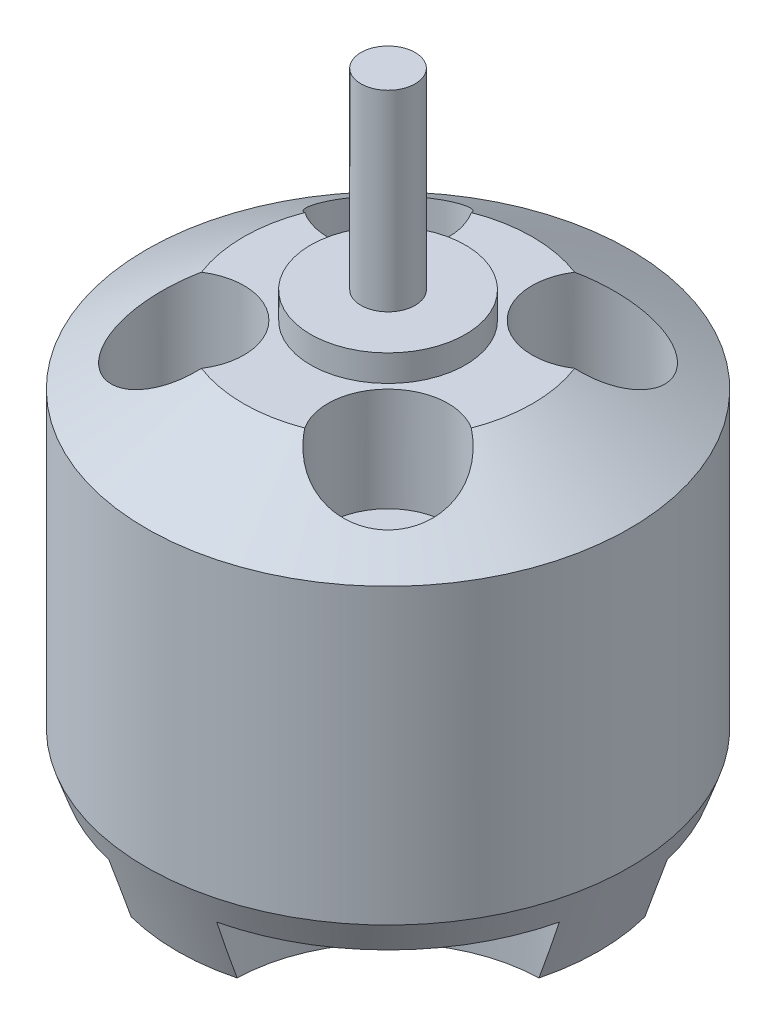
SolidWorks part; units mm, degrees
ref_plane "Front Plane" through (0, 0, 0) normal (0, 0, 1) x (1, 0, 0)
ref_plane "Top Plane" through (0, 0, 0) normal (0, 1, 0) x (1, 0, 0)
ref_plane "Right Plane" through (0, 0, 0) normal (1, 0, 0) x (0, 0, -1)
sketch "Sketch1" plane through (0, 0, 0) normal (0, 0, 1) x (1, 0, 0)
  line L0 (6.9564, -8.4455) -> (5.1721, -13.5255)
  line L1 (-6.9564, 8.4455) -> (6.9564, 8.4455)
  line L2 (-6.9564, 8.4455) -> (-6.9564, -8.4455)
  line L3 (-6.9564, -8.4455) -> (6.9564, -8.4455)
  line L4 (6.9564, 8.4455) -> (6.9564, -8.4455)
  line L5 (-6.9564, 8.4455) -> (6.9564, -8.4455) construction
  line L6 (-6.9564, -8.4455) -> (6.9564, 8.4455) construction
  line L7 (5.1721, -13.5255) -> (-6.9564, -13.5255)
  line L8 (-6.9564, -13.5255) -> (-6.9564, -8.4455)
  line L9 (6.9564, 8.4455) -> (1.3621, 11.8745)
  line L10 (1.3621, 11.8745) -> (-6.9564, 11.8745)
  line L11 (-6.9564, 11.8745) -> (-6.9564, 8.4455)
  line L12 (-6.9564, 11.8745) -> (-6.9564, 13.3985)
  line L13 (-6.9564, 13.3985) -> (-2.4987, 13.3985)
  line L14 (-2.4987, 13.3985) -> (-2.4987, 11.8745)
  line L16 (-5.3943, 13.3985) -> (-5.3943, 24.4475)
  line L17 (-5.3943, 24.4475) -> (-6.9564, 24.4475)
  line L18 (-6.9564, 24.4475) -> (-6.9564, 13.3985)
  line L19 (-6.9564, -13.5255) -> (-6.9564, -14.7955)
  line L20 (-6.9564, -14.7955) -> (-5.3943, -14.7955)
  line L21 (-5.3943, -14.7955) -> (-5.3943, -13.5255)
  point P0 (0, 0)
  dimension "D1" = 16.891
  dimension "D2" = 8.3185
  dimension "D3" = 5.08
  dimension "D4" = 25.4
  dimension "D5" = 1.524
  dimension "D6" = 11.049
  dimension "D7" = 1.27
  dimension "D8" = 13.9128
  dimension "D9" = 4.4577
  dimension "D10" = 1.5621
  dimension "D11" = 1.5621
  dimension "D12" = 12.1285
revolve "Revolve1" add sketch "Sketch1" angle 360 about L2 region at (-0.4359, -10.9275, 0) region at (0, 0, 0) region at (-1.2813, 10.0162, 0) region at (-6.1754, -14.1605, 0) region at (-4.7276, 12.6365, 0) region at (-6.1754, 18.923, 0)
sketch "Sketch2" plane through (0, -13.5255, 0) normal (0, -1, 0) x (1, 0, 0)
  line L0 (-6.9564, 11.9576) -> (-6.9564, -11.9576) construction
  line L1 (-18.914, 11.9576) -> (5.0012, 11.9576) construction
  line L2 (-18.914, 11.9576) -> (-18.914, -11.9576) construction
  line L3 (-18.914, -11.9576) -> (5.0012, -11.9576) construction
  line L4 (5.0012, 11.9576) -> (5.0012, -11.9576) construction
  line L5 (-18.914, 11.9576) -> (5.0012, -11.9576) construction
  line L6 (-18.914, -11.9576) -> (5.0012, 11.9576) construction
  line L8 (5.0012, 0) -> (-18.914, 0) construction
  circle A0 centre (5.0012, 11.9576) radius 8.9096
  circle A1 centre (-18.914, 11.9576) radius 8.9096
  circle A2 centre (-18.914, -11.9576) radius 8.9096
  circle A3 centre (5.0012, -11.9576) radius 8.9096
  circle A4 centre (-6.9564, 9.4488) radius 1.27
  circle A5 centre (2.7718, 0) radius 1.27
  circle A6 centre (-6.9564, -9.4488) radius 1.27
  circle A7 centre (-16.6846, 0) radius 1.27
  point P0 (-6.9564, 0)
  point P10 (-10.0044, 11.9576)
  point P11 (-3.9084, 11.9576)
  point P12 (-12.614, -5.6576)
  point P13 (-1.2989, 5.6576)
  dimension "D2" = 2.54
  dimension "D1" = 9.4488
  dimension "D3" = 9.4488
  dimension "D4" = 9.7282
  dimension "D5" = 9.7282
  dimension "D6" = 6.096
  dimension "D7" = 16.002
sketch "Sketch3" plane through (0, 11.8745, 0) normal (0, 1, 0) x (1, 0, 0)
  line L0 (-18.914, 11.9576) -> (5.0012, -11.9576) construction
  line L1 (-12.8365, 5.8801) -> (-1.0763, 5.8801) construction
  line L2 (-12.8365, 5.8801) -> (-12.8365, -5.8801) construction
  line L3 (-12.8365, -5.8801) -> (-1.0763, -5.8801) construction
  line L4 (-1.0763, 5.8801) -> (-1.0763, -5.8801) construction
  line L5 (-12.8365, 5.8801) -> (-1.0763, -5.8801) construction
  line L6 (-12.8365, -5.8801) -> (-1.0763, 5.8801) construction
  circle A0 centre (-1.0763, 5.8801) radius 3.4671
  circle A1 centre (-1.0763, -5.8801) radius 3.4671
  circle A2 centre (-12.8365, -5.8801) radius 3.4671
  circle A3 centre (-12.8365, 5.8801) radius 3.4671
  point P0 (-6.9564, 0)
  point P12 (-9.3694, 5.8801)
  point P13 (-4.5434, 5.8801)
  dimension "D1" = 6.9342
  dimension "D2" = 4.826
extrude "Cut-Extrude1" cut sketch "Sketch2" against normal blind 3.429
extrude "Cut-Extrude2" cut sketch "Sketch3" against normal blind 5.969
